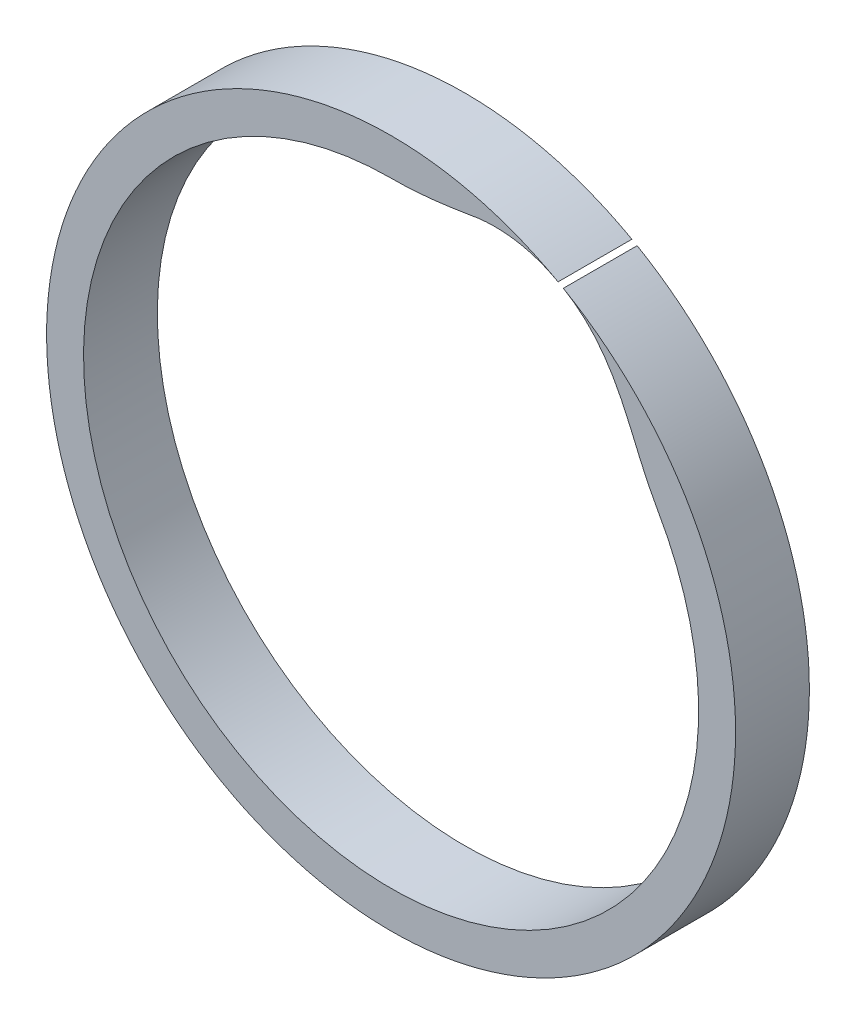
SolidWorks part; units mm, degrees
material "45"
ref_plane "前视基准面" through (0, 0, 0) normal (0, 0, 1) x (1, 0, 0)
ref_plane "上视基准面" through (0, 0, 0) normal (0, 1, 0) x (1, 0, 0)
ref_plane "右视基准面" through (0, 0, 0) normal (1, 0, 0) x (0, 0, -1)
ref_axis "基准轴1" through (0, 0, -88.99) along (0, 0, 1)
sketch "草图1" plane through (0, 0, 0) normal (0, 0, 1) x (1, 0, 0)
  arc A0 (27.1493, 48.9787) -> (28, 48.4974) centre (0, 0) ccw
  arc A1 (43.3013, 25) -> (0, 50) centre (0, 0) cw
  spline S0 degree 3 poles (0, 50) (0.5824, 50) (1.4572, 50.0134) (2.625, 50.0576) (3.5058, 50.104) (4.3914, 50.1632) (5.2831, 50.2352) (6.1821, 50.3197) (7.0896, 50.4164) (8.0068, 50.5248) (8.9348, 50.6446) (9.8749, 50.7755) (10.8281, 50.9166) (11.7957, 51.0681) (12.7778, 51.2275) (13.7681, 51.3988) (14.7688, 51.52) (15.7703, 51.5959) (16.7701, 51.6248) (17.7664, 51.6076) (18.7575, 51.5445) (19.7415, 51.4357) (20.7166, 51.2817) (21.6813, 51.083) (22.6337, 50.8402) (23.5721, 50.5537) (24.4949, 50.2243) (25.7019, 49.7288) (26.5793, 49.2947) (27.1493, 48.9787) knots 0 0 0 0 0.063089 0.094762 0.12659 0.158621 0.190907 0.223495 0.256432 0.289765 0.323539 0.357796 0.392578 0.427925 0.463876 0.500362 0.536774 0.573023 0.609123 0.645087 0.680927 0.716656 0.752287 0.787833 0.823305 0.858717 0.89408 0.929407 1 1 1 1
  spline S1 degree 3 poles (28, 48.4974) (28.5645, 48.1716) (29.3865, 47.6389) (30.4252, 46.8484) (31.1754, 46.2166) (31.8955, 45.5483) (32.585, 44.846) (33.2436, 44.1123) (33.8714, 43.3502) (34.4688, 42.5626) (35.0367, 41.7526) (35.5759, 40.9236) (36.088, 40.0786) (36.5745, 39.2208) (37.0374, 38.3535) (37.4787, 37.4796) (37.9009, 36.602) (38.3064, 35.7236) (38.698, 34.8467) (39.0784, 33.9736) (39.4504, 33.1065) (39.8169, 32.2471) (40.1808, 31.3968) (40.5449, 30.5568) (40.9117, 29.728) (41.2839, 28.9108) (41.6639, 28.1056) (42.0536, 27.3123) (42.5879, 26.2716) (43.0099, 25.5045) (43.3013, 25) knots 0 0 0 0 0.068524 0.10283 0.137186 0.171602 0.206081 0.240625 0.275225 0.309868 0.344536 0.379201 0.413835 0.448402 0.482865 0.517186 0.551325 0.585245 0.618911 0.652293 0.685366 0.718113 0.750527 0.782607 0.814365 0.845823 0.877011 0.90797 0.93875 1 1 1 1
extrude "凸台-拉伸1" add sketch "草图1" along normal blind 12
sketch "草图2" plane through (0, 0, 0) normal (0, 0, 1) x (1, 0, 0)
  line L0 (2.0864, 9.7799) -> (3.692, 12.6178)
  line L1 (3.692, 12.6178) -> (8.9141, 9.6633)
  line L2 (8.9141, 9.6633) -> (7.3085, 6.8254)
  arc A0 (2.0864, 9.7799) -> (7.3085, 6.8254) centre (0, 0) ccw
